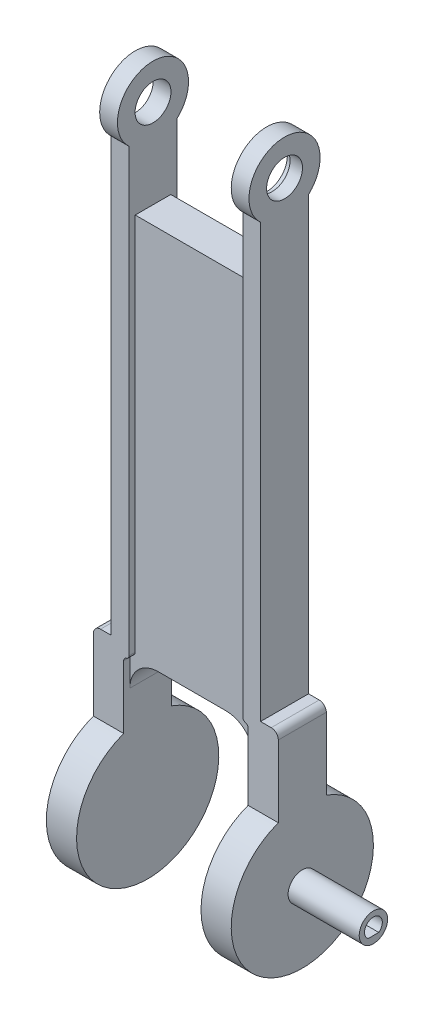
SolidWorks part; units mm, degrees
ref_plane "Alzado" through (0, 0, 0) normal (0, 0, 1) x (1, 0, 0)
ref_plane "Planta" through (0, 0, 0) normal (0, 1, 0) x (1, 0, 0)
ref_plane "Vista lateral" through (0, 0, 0) normal (1, 0, 0) x (0, 0, -1)
sketch "Croquis1" plane through (0, 0, 0) normal (0, 0, 1) x (1, 0, 0)
  line L0 (0, 0) -> (0, -143)
  line L1 (0, 0) -> (-1.6, 0)
  line L2 (-42, 0) -> (-42, -143)
  line L4 (-42, -35) -> (0, -35)
  line L5 (-42, -143) -> (0, -143)
  line L6 (-42, 0) -> (-37.4, 0)
  line L7 (-37.4, 0) -> (-37.4, -35)
  line L8 (-1.6, 0) -> (-1.6, -35)
  line L9 (-37.4, 0) -> (-42, 0)
  dimension "D1" = 42
extrude "Saliente-Extruir1" add sketch "Croquis1" against normal blind 10 contours L4 L5 region at (-21, -89, 0)
sketch "Croquis3" plane through (0, 0, 0) normal (0, 0, 1) x (1, 0, 0)
  line L0 (-47, -145) -> (-47, -160)
  line L1 (-47, -200) -> (-47, -180) construction
  line L2 (-47, -145) -> (-47, -141)
  line L4 (-47, -180) -> (-30.5, -180) construction
  line L5 (-42, -35) -> (-42, 0)
  line L6 (5, -143) -> (5, -200)
  line L7 (-47, -200) -> (-47, -180)
  line L8 (-30.5, -180) -> (-30.5, -143) construction
  line L9 (-42, -143) -> (0, -143) construction
  line L10 (-47, -180) -> (-47, -200)
  line L11 (-47, -180) -> (-47, -160)
  line L12 (-3.5, -151) -> (-3.5, -200)
  line L13 (-38.5, -200) -> (-38.5, -151)
  line L14 (5, -143) -> (5, -141)
  line L15 (-47, -200) -> (-38.5, -200)
  line L16 (-3.5, -200) -> (5, -200)
  line L17 (-45, -139) -> (-42, -139)
  line L18 (-42, -35) -> (-42, -143) construction
  line L19 (-30.5, -143) -> (-11.5, -143)
  line L20 (3, -139) -> (0, -139)
  line L21 (0, -35) -> (0, -143) construction
  line L22 (-30.5, -143) -> (-38.5, -143)
  line L23 (-38.5, -143) -> (-38.5, -151)
  line L24 (-30.5, -143) -> (-38.5, -143)
  arc A0 (5, -141) -> (3, -139) centre (3, -141) ccw
  arc A1 (-45, -139) -> (-47, -141) centre (-45, -141) ccw
  arc A2 (-11.5, -143) -> (-3.5, -151) centre (-11.5, -151) cw
  arc A3 (-38.5, -151) -> (-30.5, -143) centre (-30.5, -151) cw
  point P7 (5, -143)
  point P14 (10, -143)
  point P27 (-47, -143)
  point P29 (-49.26, -143)
  point P31 (7.26, -143)
  line M12 (-42, -35) -> (-42, -143)
  line M13 (-42, -143) -> (0, -143)
  line M14 (0, -143) -> (0, -35)
  dimension "D1" = 8.5
  dimension "D3" = 2
  dimension "D6" = 2
  dimension "D5" = 8
  dimension "D2" = 165
  dimension "D4" = 35
  dimension "D7" = 8.5
sketch "Croquis20" plane through (0, -35, 0) normal (0, 1, 0) x (1, 0, 0)
extrude "Saliente-Extruir2" add sketch "Croquis3" against normal blind 10 contours L17 A1 L2 L0 L11 L7 L15 L13 L23 M13 M12 | A2 L12 L16 L6 L14 A0 L20 M13 M14 region at (-42.813, -170.3435, 0) region at (0.6511, -169.665, 0)
sketch "Croquis21" plane through (0, 0, 0) normal (0, 0, 1) x (1, 0, 0)
  line L0 (-47, -145) -> (-47, -160)
  line L1 (-47, -200) -> (-47, -180) construction
  line L2 (-47, -145) -> (-47, -141)
  line L4 (-47, -180) -> (-30.5, -180) construction
  line L5 (-42, -35) -> (-42, 0)
  line L6 (5, -143) -> (5, -200)
  line L7 (-47, -200) -> (-47, -180)
  line L8 (-30.5, -180) -> (-30.5, -143) construction
  line L10 (-47, -180) -> (-47, -200)
  line L11 (-47, -180) -> (-47, -160)
  line L12 (-3.5, -151) -> (-3.5, -200)
  line L13 (-38.5, -200) -> (-38.5, -151)
  line L14 (5, -143) -> (5, -141)
  line L15 (-47, -200) -> (-38.5, -200)
  line L16 (-3.5, -200) -> (5, -200)
  line L17 (-45, -139) -> (-42, -139)
  line L19 (-30.5, -143) -> (-11.5, -143)
  line L20 (3, -139) -> (0, -139)
  line L22 (-30.5, -143) -> (-38.5, -143)
  line L23 (-38.5, -143) -> (-38.5, -151)
  line L24 (-30.5, -143) -> (-38.5, -143)
  arc A0 (5, -141) -> (3, -139) centre (3, -141) ccw
  arc A1 (-45, -139) -> (-47, -141) centre (-45, -141) ccw
  arc A2 (-11.5, -143) -> (-3.5, -151) centre (-11.5, -151) cw
  arc A3 (-38.5, -151) -> (-30.5, -143) centre (-30.5, -151) cw
  point P7 (5, -143)
  point P14 (10, -143)
  point P27 (-47, -143)
  point P29 (-49.26, -143)
  point P31 (7.26, -143)
  dimension "D1" = 8.5
  dimension "D3" = 2
  dimension "D6" = 2
  dimension "D5" = 8
  dimension "D4" = 35
  dimension "D7" = 8.5
extrude "Saliente-Extruir3" add sketch "Croquis21" against normal blind 10 contours L23 A3 L22 region at (-36.7131, -144.7869, 0)
sketch "Croquis22" plane through (0, 0, -10) normal (0, 0, -1) x (-1, 0, 0)
  line L0 (3.5, -156.8736) -> (3.5, -141.3338)
  line L1 (38.5, -155.5125) -> (38.5, -141.3338)
  line L2 (3.5, -151) -> (3.5, -200) construction
  line L3 (5, -139.3973) -> (5, -35)
  line L4 (42, -35) -> (0, -35) construction
  line L5 (0, -35) -> (0, -139) construction
  line L6 (5, -35) -> (0, -35)
  line L7 (38.5, -200) -> (38.5, -151) construction
  line L8 (37, -35) -> (37, -139.3973)
  line L9 (42, -35) -> (42, -139) construction
  line L10 (0, -35) -> (0, -139)
  line L11 (0, -139) -> (-3, -139)
  line L12 (45, -139) -> (42, -139) construction
  line L13 (47, -200) -> (47, -141) construction
  line L14 (47, -200) -> (38.5, -200) construction
  line L15 (3.5, -200) -> (-5, -200) construction
  line L16 (-5, -141) -> (-5, -200) construction
  line L17 (42, -35) -> (0, -35)
  line L18 (42, -35) -> (42, -139)
  line L19 (45, -139) -> (42, -139)
  line L20 (47, -200) -> (47, -141)
  line L21 (38.5, -200) -> (38.5, -151)
  line L22 (47, -200) -> (38.5, -200)
  line L23 (3.5, -200) -> (-5, -200)
  line L24 (-5, -141) -> (-5, -200)
  arc A0 (4.25, -140.3655) -> (3.5, -141.3338) centre (4.5, -141.3338) ccw
  arc A1 (4.25, -140.3655) -> (5, -139.3973) centre (4, -139.3973) ccw
  arc A2 (37.75, -140.3655) -> (37, -139.3973) centre (38, -139.3973) cw
  arc A3 (38.5, -141.3338) -> (37.75, -140.3655) centre (37.5, -141.3338) ccw
  arc A4 (47, -141) -> (45, -139) centre (45, -141) ccw construction
  arc A5 (-3, -139) -> (-5, -141) centre (-3, -141) ccw construction
  arc A6 (47, -141) -> (45, -139) centre (45, -141) ccw
  arc A7 (-3, -139) -> (-5, -141) centre (-3, -141) ccw
  line M10 (38.5, -151) -> (38.5, -200)
  line M11 (38.5, -200) -> (47, -200)
  line M12 (47, -200) -> (47, -141)
  arc M13 (47, -141) -> (45, -139) centre (45, -141) ccw
  line M14 (45, -139) -> (42, -139)
  line M15 (42, -139) -> (42, -35)
  line M16 (42, -35) -> (0, -35)
  line M17 (0, -35) -> (0, -139)
  line M18 (0, -139) -> (-3, -139)
  arc M19 (-3, -139) -> (-5, -141) centre (-3, -141) ccw
  line M20 (-5, -141) -> (-5, -200)
  line M21 (-5, -200) -> (3.5, -200)
  line M22 (3.5, -200) -> (3.5, -151)
  dimension "D2" = 1
  dimension "D3" = 1
  dimension "D5" = 1
  dimension "D6" = 1
  dimension "D1" = 5
  dimension "D4" = 5
extrude "Saliente-Extruir4" add sketch "Croquis22" along normal blind 1.75 contours A0 A1 L3 L0 M16 M17 M18 M19 M20 M21 M22 | A3 L1 L8 A2 M10 M11 M12 M13 M14 M15 M16 region at (-0.8883, -128.2038, -10) region at (-41.1117, -128.2038, -10)
sketch "Croquis24" plane through (0, 0, 0) normal (0, 0, 1) x (1, 0, 0)
  line L0 (-37, -35) -> (-37, -138.9269)
  line L1 (-42, -35) -> (0, -35) construction
  line L2 (-5, -35) -> (-5, -138.9269)
  line L3 (-42, -35) -> (-42, -139) construction
  line L4 (0, -35) -> (0, -139) construction
  line L5 (-38.5, -156.0308) -> (-38.5, -143.4351)
  line L6 (-38.5, -200) -> (-38.5, -151) construction
  line L7 (-3.5, -141.3338) -> (-3.5, -151) construction
  line L8 (-3.5, -151) -> (-3.5, -200) construction
  line L9 (-3.5, -151) -> (-3.5, -142.3338)
  line L10 (-37, -141.4986) -> (-37, -138.9269)
  line L11 (-5, -140.3973) -> (-5, -138.9269)
  line L12 (-3.5, -200) -> (5, -200) construction
  line L13 (5, -141) -> (5, -200) construction
  line L14 (3, -139) -> (0, -139) construction
  line L15 (-45, -139) -> (-42, -139) construction
  line L16 (-47, -200) -> (-47, -141) construction
  line L17 (-47, -200) -> (-38.5, -200) construction
  line L18 (-3.5, -151) -> (-3.5, -200)
  line L19 (-3.5, -200) -> (5, -200)
  line L20 (5, -141) -> (5, -200)
  line L21 (3, -139) -> (0, -139)
  line L22 (0, -35) -> (0, -139)
  line L23 (-42, -35) -> (-37, -35)
  line L24 (-42, -35) -> (-42, -139)
  line L25 (-45, -139) -> (-42, -139)
  line L26 (-47, -200) -> (-47, -141)
  line L27 (-47, -200) -> (-38.5, -200)
  line L28 (-38.5, -200) -> (-38.5, -151)
  line L29 (-5, -35) -> (0, -35)
  arc A0 (-4.25, -141.3655) -> (-5, -140.3973) centre (-4, -140.3973) cw
  arc A1 (-4.25, -141.3655) -> (-3.5, -142.3338) centre (-4.5, -142.3338) cw
  arc A2 (-37, -141.4986) -> (-37.75, -142.4669) centre (-38, -141.4986) cw
  arc A3 (-37.75, -142.4669) -> (-38.5, -143.4351) centre (-37.5, -143.4351) ccw
  arc A4 (5, -141) -> (3, -139) centre (3, -141) ccw construction
  arc A5 (-45, -139) -> (-47, -141) centre (-45, -141) ccw construction
  arc A6 (5, -141) -> (3, -139) centre (3, -141) ccw
  arc A7 (-45, -139) -> (-47, -141) centre (-45, -141) ccw
  point P28 (-37, -142.4986)
  line M6 (-3.5, -151) -> (-3.5, -200)
  line M7 (-3.5, -200) -> (5, -200)
  line M8 (5, -200) -> (5, -141)
  arc M9 (5, -141) -> (3, -139) centre (3, -141) ccw
  line M10 (3, -139) -> (0, -139)
  line M11 (0, -139) -> (0, -35)
  line M12 (0, -35) -> (-42, -35)
  line M13 (-42, -35) -> (-42, -139)
  line M14 (-42, -139) -> (-45, -139)
  arc M15 (-45, -139) -> (-47, -141) centre (-45, -141) ccw
  line M16 (-47, -141) -> (-47, -200)
  line M17 (-47, -200) -> (-38.5, -200)
  line M18 (-38.5, -200) -> (-38.5, -151)
  dimension "D3" = 1
  dimension "D4" = 1
  dimension "D5" = 1
  dimension "D6" = 1
  dimension "D1" = 5
  dimension "D2" = 5
extrude "Saliente-Extruir5" add sketch "Croquis24" along normal blind 1.75 contours A3 A2 L10 L0 L5 M12 M13 M14 M15 M16 M17 M18 | A0 A1 L9 L2 L11 M6 M7 M8 M9 M10 M11 M12 region at (-41.1016, -128.2438, 0) region at (-0.8931, -128.2221, 0)
ref_plane "Plano1" through (0, -35, 1.75) normal (0, 0, 1) x (1, 0, 0)
sketch "Croquis26" plane through (0, 0, 0) normal (0, 0, 1) x (1, 0, 0)
  line L4 (-42, -35) -> (-37, -35)
  line L5 (-42, -35) -> (-42, 0)
  line L6 (-42, 0) -> (-37, 0)
  line L7 (-37, -35) -> (-37, 0)
  line L8 (-5, -35) -> (0, -35)
  line L9 (-5, -35) -> (-5, 0)
  line L10 (-5, 0) -> (0, 0)
  line L11 (0, -35) -> (0, 0)
  dimension "D1" = 35
  dimension "D2" = 35
extrude "Saliente-Extruir6" add sketch "Croquis26" along normal up to surface (1.75 mm away) up to face at (-41.2164, -131.5986, 1.75)
sketch "Croquis27" plane through (0, 0, 0) normal (0, 0, -1) x (-1, 0, 0)
  line L1 (0, 0) -> (5, 0)
  line L2 (0, 0) -> (0, -35)
  line L3 (0, -35) -> (5, -35)
  line L4 (5, 0) -> (5, -35)
  line L5 (37, 0) -> (42, 0)
  line L6 (37, 0) -> (37, -35)
  line L7 (37, -35) -> (42, -35)
  line L8 (42, 0) -> (42, -35)
extrude "Saliente-Extruir7" add sketch "Croquis27" along normal up to surface (11.75 mm away) up to face at (-0.7836, -130.9682, -11.75)
sketch "Croquis28" plane through (-5, 0, 0) normal (-1, 0, 0) x (0, 0, 1)
  line L0 (-5, 0) -> (-5, -20) construction
  line L1 (1.75, 0) -> (-11.75, 0) construction
  line L2 (1.75, 0) -> (1.75, -140.3973) construction
  line L3 (1.75, 0) -> (1.75, -140.3973)
  line L4 (1.75, 0) -> (-11.75, 0)
  circle A0 centre (-5, -10) radius 10
  line M7 (1.75, -140.3973) -> (1.75, 0)
  line M8 (1.75, 0) -> (-11.75, 0)
  line M9 (-11.75, 0) -> (-11.75, -139.3973)
  dimension "D1" = 20
extrude "Cortar-Extruir3" cut sketch "Croquis28" against normal blind 99.75 and the other way through all contours A0 L4 M9 | A0 M7 M8 region at (-5, -0.7651, 0.1099) region at (-5, -0.7651, -10.1099)
extrude "Saliente-Extruir8" add sketch "Croquis28<5>" against normal up to surface (5 mm away) contours A0 M9 | L3 A0 region at (-5, -10, 3.07) region at (-5, -10, -13.07) up to face at (0, -70.1555, -5)
sketch "Croquis28<5>" plane through (-5, 0, 0) normal (-1, 0, 0) x (0, 0, 1) same geometry as "Croquis28"
sketch "Croquis29" plane through (-37, 0, 0) normal (1, 0, 0) x (0, 0, -1)
  line L0 (5, 0) -> (5, -20) construction
  arc A0 (11.75, -2.6218) -> (-1.75, -2.6218) centre (5, -10) ccw construction
  circle A1 centre (5, -10) radius 10
  dimension "D2" = 20
  dimension "D1" = 20
extrude "Saliente-Extruir9" add sketch "Croquis29" against normal up to surface (5 mm away) up to face at (-42, -70.1555, -5)
sketch "Croquis31" plane through (-38.5, 0, 0) normal (1, 0, 0) x (0, 0, -1)
  line L0 (5, -200) -> (5, -160) construction
  line L1 (11.75, -200) -> (-1.75, -200) construction
  line L2 (11.75, -200) -> (11.75, -141.3338) construction
  line L3 (-1.75, -200) -> (-1.75, -143.4351) construction
  line L4 (11.75, -198.8265) -> (11.75, -141.3338)
  line L5 (11.75, -200) -> (11.75, -141.3338)
  line L6 (-1.75, -198.8265) -> (-1.75, -143.4351)
  line L7 (11.75, -200) -> (-1.75, -200)
  line L8 (-1.75, -200) -> (-1.75, -143.4351)
  circle A0 centre (5, -180) radius 20
  line M5 (-1.75, -143.4351) -> (-1.75, -200)
  line M6 (-1.75, -200) -> (11.75, -200)
  line M7 (11.75, -200) -> (11.75, -141.3338)
  dimension "D2" = 40
  dimension "D1" = 40
extrude "Cortar-Extruir5" cut sketch "Croquis31" along normal through all both and the other way through all contours A0 M5 M6 | A0 L7 M7 region at (-38.5, -199.6498, -10.0726) region at (-38.5, -199.6498, 0.0726)
sketch "Croquis32" plane through (-38.5, 0, 0) normal (1, 0, 0) x (0, 0, -1)
  line L0 (5, -200) -> (5, -160) construction
  arc A0 (-1.75, -198.8265) -> (11.75, -198.8265) centre (5, -180) ccw construction
  circle A1 centre (5, -180) radius 20
  dimension "D1" = 40
extrude "Saliente-Extruir11" add sketch "Croquis32" against normal up to surface (8.5 mm away) up to face at (-47, -170.2066, -5)
sketch "Croquis33" plane through (-3.5, 0, 0) normal (-1, 0, 0) x (0, 0, 1)
  line L0 (-5, -200) -> (-5, -160) construction
  arc A0 (-11.75, -198.8265) -> (1.75, -198.8265) centre (-5, -180) ccw construction
  circle A1 centre (-5, -180) radius 20
  dimension "D1" = 40
extrude "Saliente-Extruir12" add sketch "Croquis33" against normal up to surface (8.5 mm away) up to face at (5, -170.2066, -5)
sketch "Croquis34" plane through (-42, 0, 0) normal (-1, 0, 0) x (0, 0, 1)
  circle A0 centre (-5, -10) radius 5.05
  dimension "D1" = 10.1
extrude "Cortar-Extruir6" cut sketch "Croquis34" against normal blind 90
sketch "Croquis39" plane through (-5, 0, 0) normal (-1, 0, 0) x (0, 0, 1)
  circle A0 centre (-5, -10) radius 5.78
  dimension "D1" = 11.56
extrude "Cortar-Extruir7" cut sketch "Croquis39" against normal blind 1.5
sketch "Croquis40" plane through (5, 0, 0) normal (1, 0, 0) x (0, 0, -1)
  line L0 (3.5, -182) -> (6.5, -182)
  circle A0 centre (5, -180) radius 4
  circle A1 centre (5, -180) radius 2.5
  dimension "D1" = 5
  dimension "D2" = 8
  dimension "D3" = 2
extrude "Saliente-Extruir13" add sketch "Croquis40" along normal blind 20 contours A0 A1 | L0 A1 region at (5, -182.2018, -5) region at (5, -180, -1.1131)
sketch "Croquis41" plane through (0, -182, 0) normal (0, 1, 0) x (1, 0, 0)
  line L0 (5, 1) -> (25, 1) construction
  circle A0 centre (18.0487, 5) radius 1.5
  circle A1 centre (12.0487, 5) radius 1.5
  dimension "D1" = 3
  dimension "D2" = 3
  dimension "D3" = 6
  dimension "D4" = 4
extrude "Cortar-Extruir8" cut sketch "Croquis41" against normal blind 20
